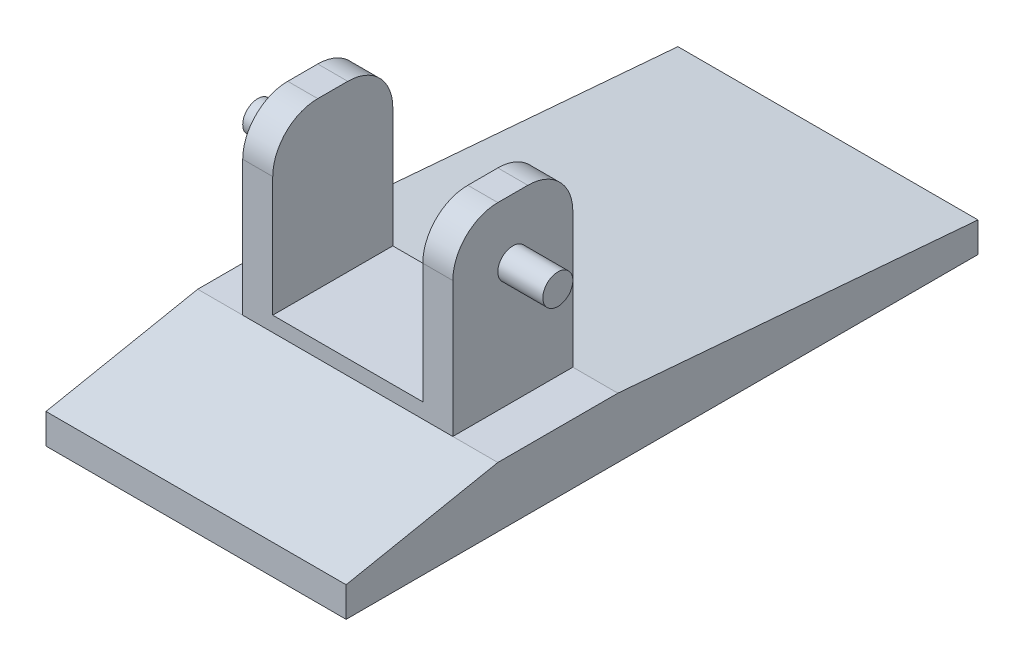
SolidWorks part; units mm, degrees
ref_plane "Front Plane" through (0, 0, 0) normal (0, 0, 1) x (1, 0, 0)
ref_plane "Top Plane" through (0, 0, 0) normal (0, 1, 0) x (1, 0, 0)
ref_plane "Right Plane" through (0, 0, 0) normal (1, 0, 0) x (0, 0, -1)
sketch "Sketch1" plane through (0, 0, 0) normal (1, 0, 0) x (0, 0, -1)
  line L1 (0, 20.0763) -> (0, -18.8747) construction
  line L3 (-5, 61.1253) -> (5, 61.1253)
  line L4 (-20, 46.1253) -> (-20, 1.1253)
  line L6 (20, 46.1253) -> (20, 1.1253)
  line L11 (-20, 1.1253) -> (-70.5498, -8.8747)
  line L12 (-20, 6.2666) -> (-20, -80.485) construction
  line L13 (-70.5498, -8.8747) -> (-70.5498, -18.8747)
  line L14 (-70.5498, -18.8747) -> (140, -18.8747)
  line L15 (20, 1.1253) -> (140, -8.8747)
  line L16 (140, -8.8747) -> (140, -18.8747)
  arc A0 (5, 61.1253) -> (20, 46.1253) centre (5, 46.1253) cw
  arc A1 (-5, 61.1253) -> (-20, 46.1253) centre (-5, 46.1253) ccw
  point P17 (20, 61.1253)
  point P20 (-20, 61.1253)
  dimension "D10" = 15
  dimension "D11" = 15
  dimension "D1" = 40
  dimension "D2" = 60
  dimension "D3" = 20
  dimension "D4" = 10
  dimension "D5" = 10
  dimension "D6" = 10
  dimension "D7" = 10
extrude "Boss-Extrude1" add sketch "Sketch1" along normal blind 10
sketch "Sketch2" plane through (10, 0, 0) normal (1, 0, 0) x (0, 0, -1)
  line L2 (140, -18.8747) -> (140, -8.8747) construction
  line L3 (140, -8.8747) -> (140, -18.8747)
  line L4 (140, -18.8747) -> (-70.5498, -18.8747)
  line L5 (-70.5498, -18.8747) -> (-70.5498, -8.8747)
  line L6 (-20, 1.1253) -> (20, 1.1253)
  line L7 (20, 1.1253) -> (140, -8.8747)
  line L8 (-70.5498, -8.8747) -> (-20, 1.1253)
sketch "Sketch3" plane through (0, 0, 0) normal (-1, 0, 0) x (0, 0, 1)
  line L1 (20, 1.1253) -> (70.5498, -8.8747)
  line L2 (70.5498, -8.8747) -> (70.5498, -18.8747)
  line L3 (70.5498, -18.8747) -> (-140, -18.8747)
  line L4 (-140, -18.8747) -> (-140, -8.8747)
  line L5 (-140, -8.8747) -> (-20, 1.1253)
  line L6 (-20, 1.1253) -> (-20, 6.1253)
  line L7 (-20, 1.1253) -> (-20, 46.1253) construction
  line L8 (-20, 6.1253) -> (20, 6.1253)
  line L9 (20, 46.1253) -> (20, 1.1253) construction
  line L10 (20, 6.1253) -> (20, 1.1253)
  dimension "D1" = 5
extrude "Boss-Extrude3" add sketch "Sketch3" along normal blind 25
sketch "Sketch4" plane through (10, 0, 0) normal (1, 0, 0) x (0, 0, -1)
  line L0 (0, -29.5068) -> (0, 72.9739) construction
  line L2 (5, 61.1253) -> (-5, 61.1253) construction
  circle A0 centre (0, 41.1253) radius 5
  dimension "D1" = 20
extrude "Boss-Extrude4" add sketch "Sketch4" along normal blind 15
sketch "Sketch7" plane through (10, 0, 0) normal (1, 0, 0) x (0, 0, -1)
  line L0 (-70.5498, -8.8747) -> (-20, 1.1253)
  line L1 (-20, 1.1253) -> (20, 1.1253)
  line L2 (20, 1.1253) -> (140, -8.8747)
  line L3 (140, -8.8747) -> (140, -18.8747)
  line L4 (140, -18.8747) -> (-70.5498, -18.8747)
  line L5 (-70.5498, -18.8747) -> (-70.5498, -8.8747)
extrude "Boss-Extrude6" add sketch "Sketch7" along normal blind 15
mirror "Mirror2" about plane through (-25, 0, 0) normal (1, 0, 0) of "Boss-Extrude1", "Boss-Extrude3", "Boss-Extrude4", "Boss-Extrude6"
